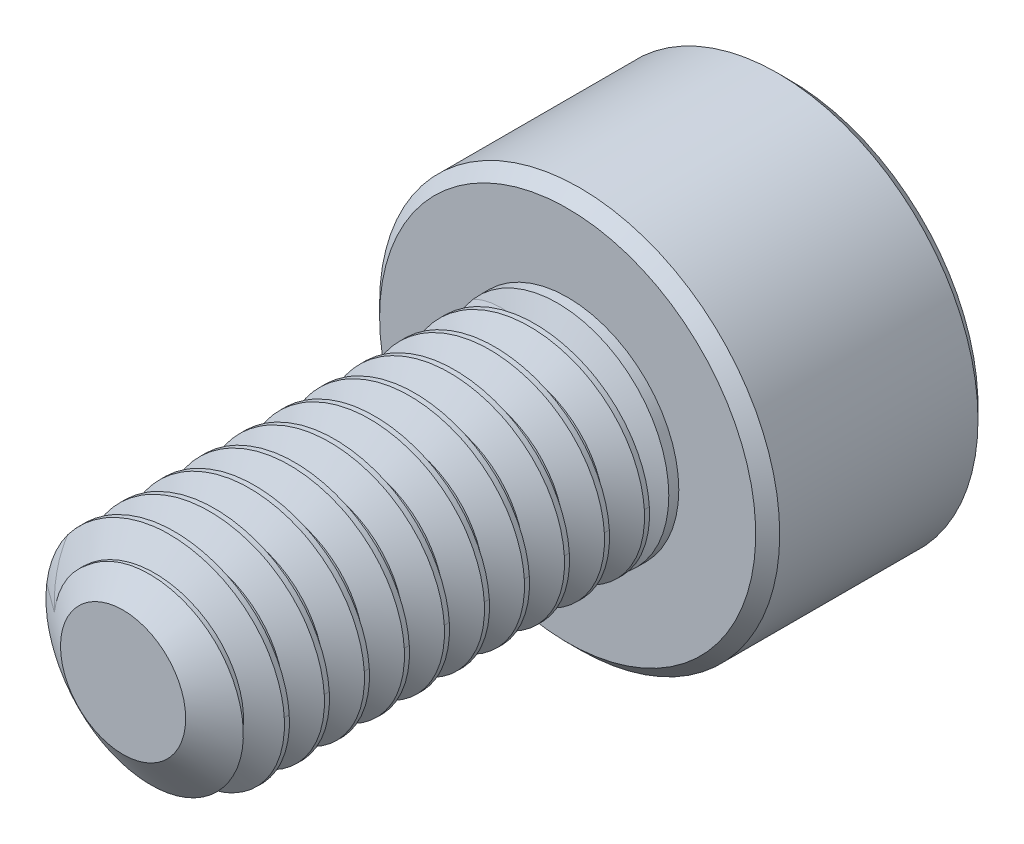
SolidWorks part; units mm, degrees
ref_plane "Front Plane" through (0, 0, 0) normal (0, 0, 1) x (1, 0, 0)
ref_plane "Top Plane" through (0, 0, 0) normal (0, 1, 0) x (1, 0, 0)
ref_plane "Right Plane" through (0, 0, 0) normal (1, 0, 0) x (0, 0, -1)
sketch "Sketch1" plane through (0, 0, 0) normal (0, 0, 1) x (1, 0, 0)
  circle A0 centre (0, 0) radius 1.25
  dimension "OD" = 2.5
extrude "Extrude1" add sketch "Sketch1" against normal blind 5
sketch "Sketch2" plane through (0, 0, 0) normal (0, 0, 1) x (1, 0, 0)
  circle A0 centre (0, 0) radius 1.25 construction
  circle A1 centre (0, 0) radius 1.25
curve "Helix/Spiral1" pitch 0.45 height 5.45 radius 1.25 centre (0, 0, 0) axis (0, 0, -1) start towards (0, 1, 0) parameters "pitch"=0.45
sketch "Sketch3" plane through (0, 0, 0) normal (1, 0, 0) x (0, 0, -1)
  line L0 (-0.3938, 1.25) -> (-0.225, 0.9577)
  line L1 (-0.225, 0.9577) -> (-0.1688, 0.9577)
  line L2 (-0.1688, 0.9577) -> (0, 1.25)
  line L3 (-0.3938, 1.25) -> (0, 1.25)
  line L4 (-0.1969, 1.25) -> (-0.1969, 0.9577) construction
  line L5 (-0.3094, 1.1039) -> (-0.0844, 1.1039) construction
  line L6 (0, 1.25) -> (0, -1.25) construction
  line L7 (0, -1.25) -> (5, -1.25) construction
  point P11 (2.025, -1.25)
  dimension "D1" = 0.0563
  dimension "D2" = 0.225
  dimension "D3" = 60
  dimension "D4" = 2.025
sweep "Cut-Sweep1" cut profiles "Sketch3" path "Helix/Spiral1" align with end faces yes
sketch "Sketch4" plane through (0, 0, 0) normal (1, 0, 0) x (0, 0, -1)
  line L0 (0.3825, 1.25) -> (0, 0.7037)
  line L1 (0, 0.7037) -> (0, 1.25)
  line L2 (0.3825, 1.25) -> (0, 1.25)
  line L3 (-0.3938, 1.25) -> (0, 1.25) construction
  line L4 (0, 0) -> (7.0209, 0) construction
  dimension "D1" = 55
  dimension "D2" = 0.254
revolve "Cut-Revolve1" cut sketch "Sketch4" angle 360 about L4
sketch "Sketch5" plane through (0, 0, 0) normal (1, 0, 0) x (0, 0, -1)
  line L0 (5, -0.738) -> (5, 1.2445) construction
  line L1 (5, 1.25) -> (0.1203, 1.25)
  line L2 (5, 1.25) -> (5, 0)
  line L3 (5, 0) -> (0.0001, 0)
  line L4 (0.0001, 0.9198) -> (0.0001, 0)
  line L5 (0.1203, 1.25) -> (0.0001, 0.9198)
  line L6 (0, 0) -> (9.9695, 0) construction
  point P3 (0.0001, 1.25)
  point P10 (0.0001, 1.25)
  dimension "D1" = 0.3302
  dimension "Thread min" = 0.0001
  dimension "D3" = 20
revolve "partially thread" [suppressed] add sketch "Sketch5" angle 360 about L6
sketch "Sketch6" plane through (0, 0, -5) normal (0, 0, -1) x (-1, 0, 0)
  circle A0 centre (0, 0) radius 2.25
  dimension "head dia" = 4.5
extrude "Extrude2" add sketch "Sketch6" along normal blind 2.5
sketch "Sketch7" plane through (0, 0, -7.5) normal (0, 0, -1) x (-1, 0, 0)
  line L1 (0, 1.1547) -> (-1, 0.5774)
  line L2 (-1, 0.5774) -> (-1, -0.5774)
  line L3 (-1, -0.5774) -> (0, -1.1547)
  line L4 (0, -1.1547) -> (1, -0.5774)
  line L5 (1, -0.5774) -> (1, 0.5774)
  line L6 (1, 0.5774) -> (0, 1.1547)
  circle A0 centre (0, 0) radius 1 construction
  dimension "hex dia" = 2
extrude "Cut-Extrude1" cut sketch "Sketch7" against normal blind 1.5
sketch "Sketch8" plane through (0, 0, -7.5) normal (0, 0, -1) x (-1, 0, 0)
  circle A0 centre (0, 0) radius 1.1547
extrude "Cut-Extrude2" cut sketch "Sketch8" against normal through all draft 45
chamfer "Chamfer1" distance 0.135 angle 45 2 edges at (-2.25, 0, -7.5) (-2.25, 0, -5)
sketch "Sketch9" plane through (0, 0, 0) normal (1, 0, 0) x (0, 0, -1)
  line L0 (0, 1.25) -> (0, -1.25) construction
  line L1 (2.475, 1.25) -> (2.475, -1.25) construction
  dimension "D1" = 2.475
sketch "Sketch10" plane through (0, 0, 0) normal (1, 0, 0) x (0, 0, -1)
  line L0 (5, 1.25) -> (5, 0)
  line L1 (5, 1.25) -> (4.8875, 1.25)
  line L2 (4.8875, 1.25) -> (4.3697, 0)
  line L3 (5, 0) -> (4.3697, 0)
  line L4 (5, 2.115) -> (5, -2.115) construction
  dimension "D1" = 22.5
  dimension "D2" = 0.1125
revolve "Revolve1" add sketch "Sketch10" angle 360 about L3
equation "\"D3@Helix/Spiral1\" = \"screw length@Extrude1\"+\"pitch@Helix/Spiral1\""
equation "\"D1@Sketch3\" = \"pitch@Helix/Spiral1\"*.125"
equation "\"D2@Sketch3\" = \"pitch@Helix/Spiral1\"*.5"
equation "\"D1@Cut-Extrude1\" = \"hex dia@Sketch7\"*.75"
equation "\"D1@Chamfer1\" = \"head dia@Sketch6\"*.03"
equation "\"D1@Sketch9\" = \"pitch@Helix/Spiral1\"*5.5"
equation "\"D2@Sketch10\" = \"pitch@Helix/Spiral1\"*.25"
equation "\"D4@Sketch3\" = \"pitch@Helix/Spiral1\"*4.50"
